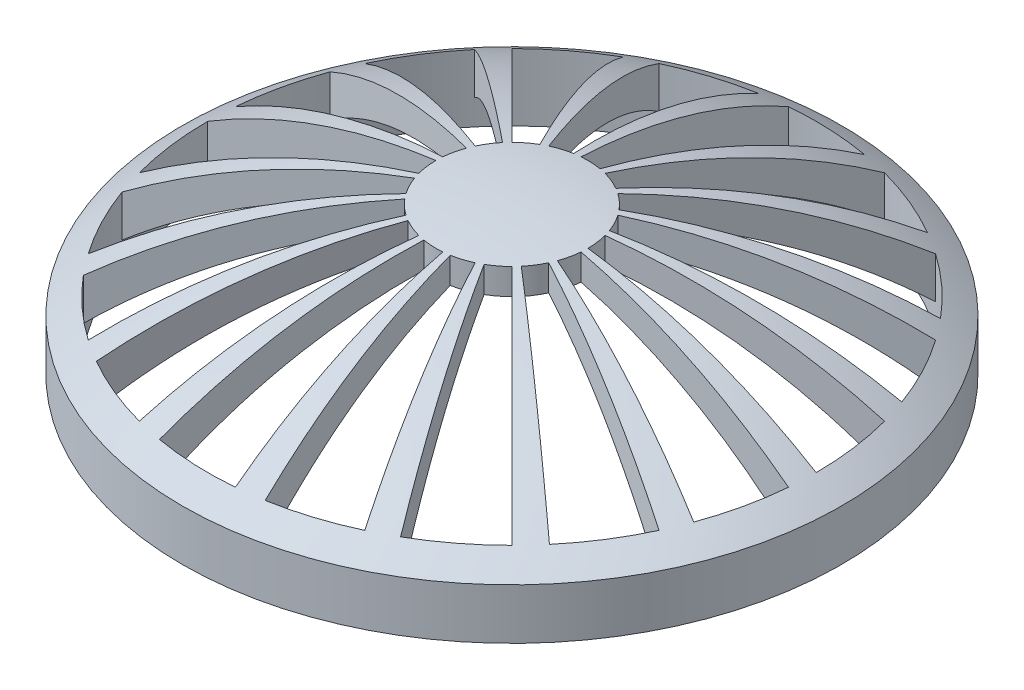
SolidWorks part; units mm, degrees
ref_plane "Front Plane" through (0, 0, 0) normal (0, 0, 1) x (1, 0, 0)
ref_plane "Top Plane" through (0, 0, 0) normal (0, 1, 0) x (1, 0, 0)
ref_plane "Right Plane" through (0, 0, 0) normal (1, 0, 0) x (0, 0, -1)
sketch "Sketch1" plane through (0, 0, 0) normal (0, 1, 0) x (1, 0, 0)
  circle A0 centre (0, 0) radius 32.5
  dimension "D1" = 65
extrude "Boss-Extrude1" add sketch "Sketch1" along normal blind 5
dome "Dome1" faces to dome 1 distance 10 reverse direction no elliptical dome no face at (0, 5, 32.5) parameters "D1"=10
sketch "Sketch2" plane through (0, 0, 0) normal (0, -1, 0) x (-1, 0, 0)
  circle A0 centre (0, 0) radius 30
  dimension "D1" = 60
extrude "Cut-Extrude1" cut sketch "Sketch2" against normal blind 2.5
dome "Dome6" faces to dome 1 distance 10 reverse direction yes elliptical dome no face at (0, 2.5, -30) parameters "D1"=10
sketch "Sketch4" plane through (0, 0, 0) normal (0, -1, 0) x (1, 0, 0)
  line L0 (-7.5, 0) -> (-30, 0)
  line L1 (-7.2444, 1.9411) -> (-28.9778, 7.7646)
  line L2 (-7.0477, 2.5652) -> (-28.1908, 10.2606)
  line L3 (-6.1436, 4.3018) -> (-24.5746, 17.2073)
  line L4 (-5.7453, 4.8209) -> (-22.9813, 19.2836)
  line L5 (-4.3018, 6.1436) -> (-17.2073, 24.5746)
  line L6 (-3.75, 6.4952) -> (-15, 25.9808)
  line L7 (-1.9411, 7.2444) -> (-7.7646, 28.9778)
  line L8 (-1.3024, 7.3861) -> (-5.2094, 29.5442)
  line L9 (0.6537, 7.4715) -> (2.6147, 29.8858)
  line L10 (1.3024, 7.3861) -> (5.2094, 29.5442)
  line L11 (3.1696, 6.7973) -> (12.6785, 27.1892)
  line L12 (3.75, 6.4952) -> (15, 25.9808)
  line L13 (5.3033, 5.3033) -> (21.2132, 21.2132)
  line L14 (5.7453, 4.8209) -> (22.9813, 19.2836)
  line L15 (6.7973, 3.1696) -> (27.1892, 12.6785)
  line L16 (7.0477, 2.5652) -> (28.1908, 10.2606)
  line L17 (7.4715, 0.6537) -> (29.8858, 2.6147)
  line L18 (7.5, 0) -> (30, 0)
  line L19 (7.2444, -1.9411) -> (28.9778, -7.7646)
  line L20 (7.0477, -2.5652) -> (28.1908, -10.2606)
  line L21 (6.1436, -4.3018) -> (24.5746, -17.2073)
  line L22 (5.7453, -4.8209) -> (22.9813, -19.2836)
  line L23 (4.3018, -6.1436) -> (17.2073, -24.5746)
  line L24 (3.75, -6.4952) -> (15, -25.9808)
  line L25 (1.9411, -7.2444) -> (7.7646, -28.9778)
  line L26 (1.3024, -7.3861) -> (5.2094, -29.5442)
  line L27 (-0.6537, -7.4715) -> (-2.6147, -29.8858)
  line L28 (-1.3024, -7.3861) -> (-5.2094, -29.5442)
  line L29 (-3.1696, -6.7973) -> (-12.6785, -27.1892)
  line L30 (-3.75, -6.4952) -> (-15, -25.9808)
  line L31 (-5.3033, -5.3033) -> (-21.2132, -21.2132)
  line L32 (-5.7453, -4.8209) -> (-22.9813, -19.2836)
  line L33 (-6.7973, -3.1696) -> (-27.1892, -12.6785)
  line L34 (-7.0477, -2.5652) -> (-28.1908, -10.2606)
  line L35 (-7.4715, -0.6537) -> (-29.8858, -2.6147)
  arc A0 (-28.9778, 7.7646) -> (-30, 0) centre (0, 0) ccw
  arc A1 (-7.2444, 1.9411) -> (-7.5, 0) centre (0, 0) ccw
  arc A2 (-24.5746, 17.2073) -> (-28.1908, 10.2606) centre (0, 0) ccw
  arc A3 (-6.1436, 4.3018) -> (-7.0477, 2.5652) centre (0, 0) ccw
  arc A4 (-17.2073, 24.5746) -> (-22.9813, 19.2836) centre (0, 0) ccw
  arc A5 (-4.3018, 6.1436) -> (-5.7453, 4.8209) centre (0, 0) ccw
  arc A6 (-7.7646, 28.9778) -> (-15, 25.9808) centre (0, 0) ccw
  arc A7 (-1.9411, 7.2444) -> (-3.75, 6.4952) centre (0, 0) ccw
  arc A8 (2.6147, 29.8858) -> (-5.2094, 29.5442) centre (0, 0) ccw
  arc A9 (0.6537, 7.4715) -> (-1.3024, 7.3861) centre (0, 0) ccw
  arc A10 (12.6785, 27.1892) -> (5.2094, 29.5442) centre (0, 0) ccw
  arc A11 (3.1696, 6.7973) -> (1.3024, 7.3861) centre (0, 0) ccw
  arc A12 (21.2132, 21.2132) -> (15, 25.9808) centre (0, 0) ccw
  arc A13 (5.3033, 5.3033) -> (3.75, 6.4952) centre (0, 0) ccw
  arc A14 (27.1892, 12.6785) -> (22.9813, 19.2836) centre (0, 0) ccw
  arc A15 (6.7973, 3.1696) -> (5.7453, 4.8209) centre (0, 0) ccw
  arc A16 (29.8858, 2.6147) -> (28.1908, 10.2606) centre (0, 0) ccw
  arc A17 (7.4715, 0.6537) -> (7.0477, 2.5652) centre (0, 0) ccw
  arc A18 (28.9778, -7.7646) -> (30, 0) centre (0, 0) ccw
  arc A19 (7.2444, -1.9411) -> (7.5, 0) centre (0, 0) ccw
  arc A20 (24.5746, -17.2073) -> (28.1908, -10.2606) centre (0, 0) ccw
  arc A21 (6.1436, -4.3018) -> (7.0477, -2.5652) centre (0, 0) ccw
  arc A22 (17.2073, -24.5746) -> (22.9813, -19.2836) centre (0, 0) ccw
  arc A23 (4.3018, -6.1436) -> (5.7453, -4.8209) centre (0, 0) ccw
  arc A24 (7.7646, -28.9778) -> (15, -25.9808) centre (0, 0) ccw
  arc A25 (1.9411, -7.2444) -> (3.75, -6.4952) centre (0, 0) ccw
  arc A26 (-2.6147, -29.8858) -> (5.2094, -29.5442) centre (0, 0) ccw
  arc A27 (-0.6537, -7.4715) -> (1.3024, -7.3861) centre (0, 0) ccw
  arc A28 (-12.6785, -27.1892) -> (-5.2094, -29.5442) centre (0, 0) ccw
  arc A29 (-3.1696, -6.7973) -> (-1.3024, -7.3861) centre (0, 0) ccw
  arc A30 (-21.2132, -21.2132) -> (-15, -25.9808) centre (0, 0) ccw
  arc A31 (-5.3033, -5.3033) -> (-3.75, -6.4952) centre (0, 0) ccw
  arc A32 (-27.1892, -12.6785) -> (-22.9813, -19.2836) centre (0, 0) ccw
  arc A33 (-6.7973, -3.1696) -> (-5.7453, -4.8209) centre (0, 0) ccw
  arc A34 (-29.8858, -2.6147) -> (-28.1908, -10.2606) centre (0, 0) ccw
  arc A35 (-7.4715, -0.6537) -> (-7.0477, -2.5652) centre (0, 0) ccw
  dimension "D1" = 15
  dimension "D2" = 15
extrude "Cut-Extrude3" cut sketch "Sketch4" against normal through all
